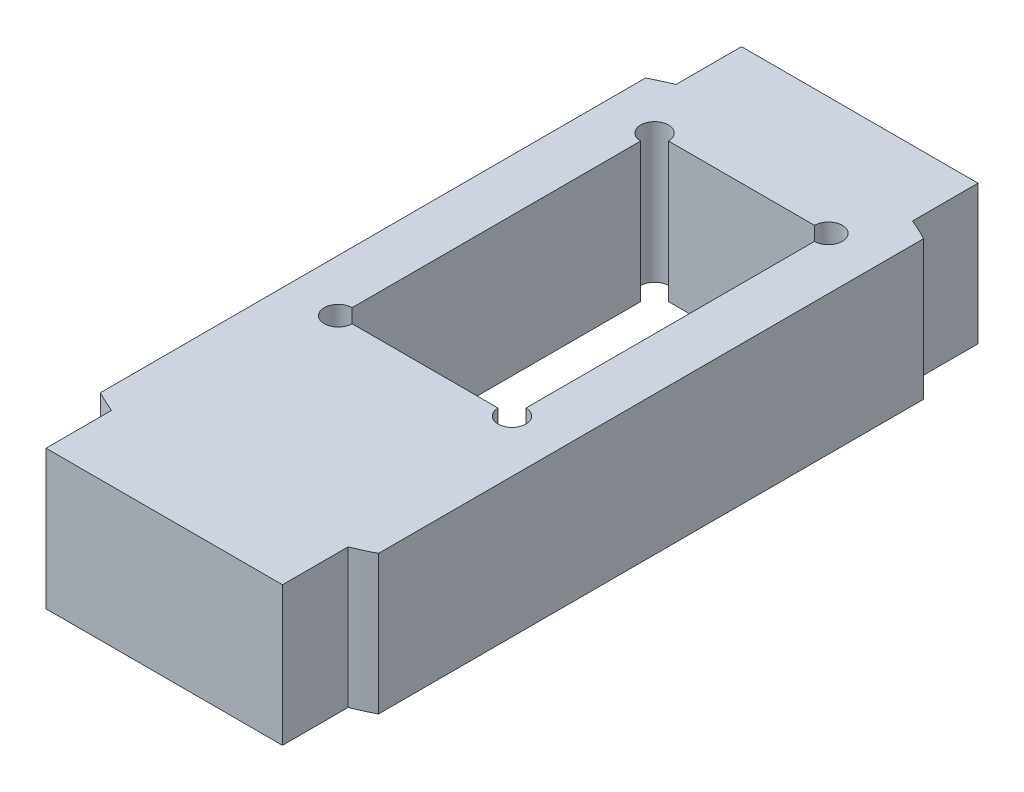
SolidWorks part; units mm, degrees
material "PE Alta Densidade"
ref_plane "Front" through (0, 0, 0) normal (0, 0, 1) x (1, 0, 0)
ref_plane "Top" through (0, 0, 0) normal (0, 1, 0) x (1, 0, 0)
ref_plane "Right" through (0, 0, 0) normal (1, 0, 0) x (0, 0, -1)
sketch "Esboço1" plane through (0, 0, 0) normal (0, 1, 0) x (1, 0, 0)
  line L0 (-8.5, 20.2916) -> (-8.5, 25)
  line L1 (-8.5, -25) -> (8.5, -25)
  line L2 (-8.5, -25) -> (-8.5, -20.2916)
  line L3 (-8.5, 25) -> (8.5, 25)
  line L4 (8.5, -25) -> (8.5, -20.2916)
  line L5 (0, 94.3548) -> (0, -102.4194) construction
  line L6 (8.5, 20.2916) -> (8.5, 25)
  line L7 (-104.5161, 0) -> (103.2258, 0) construction
  line L8 (-10, -19.5959) -> (-10, 19.5959)
  line L9 (10, -19.5959) -> (10, 19.5959)
  arc A0 (-8.5, 20.2916) -> (-10, 19.5959) centre (0, 0) ccw
  arc A1 (8.5, -20.2916) -> (10, -19.5959) centre (0, 0) ccw
  arc A2 (-8.5, 20.2916) -> (-8.5, -20.2916) centre (0, 0) ccw construction
  arc A3 (8.5, 23.5106) -> (-8.5, 23.5106) centre (0, 0) ccw construction
  arc A4 (-10, -19.5959) -> (-8.5, -20.2916) centre (0, 0) ccw
  arc A5 (10, 19.5959) -> (8.5, 20.2916) centre (0, 0) ccw
  dimension "D1" = 17
  dimension "D2" = 10
extrude "Ressalto-extrusão1" add sketch "Esboço1" along normal blind 10
sketch "Esboço2" plane through (0, 10, 0) normal (0, 1, 0) x (1, 0, 0)
  line L0 (-6.25, -5.95) -> (-6.25, 16.2) construction
  line L2 (5.25, 16.5) -> (-5.25, 16.5)
  line L3 (6.25, 15.5) -> (6.25, -5.25)
  line L4 (5.25, -6.25) -> (-5.25, -6.25)
  line L5 (-6.25, 15.5) -> (-6.25, -5.25)
  line L6 (-5.95, 16.5) -> (5.95, 16.5) construction
  line L7 (6.25, 16.2) -> (6.25, -5.95) construction
  line L8 (5.95, -6.25) -> (-5.95, -6.25) construction
  line L9 (-6.25, -6.25) -> (6.25, -6.25) construction
  line L10 (-6.25, -6.25) -> (-6.25, 16.5) construction
  line L11 (-6.25, 16.5) -> (6.25, 16.5) construction
  line L12 (6.25, -6.25) -> (6.25, 16.5) construction
  arc A0 (-6.25, -5.25) -> (-5.25, -6.25) centre (-6.25, -6.25) ccw
  arc A1 (-5.25, 16.5) -> (-6.25, 15.5) centre (-6.25, 16.5) ccw
  arc A2 (6.25, 15.5) -> (5.25, 16.5) centre (6.25, 16.5) ccw
  arc A3 (5.25, -6.25) -> (6.25, -5.25) centre (6.25, -6.25) ccw
  dimension "D1" = 2
extrude "Corte-extrusão1" cut sketch "Esboço2" against normal through all
